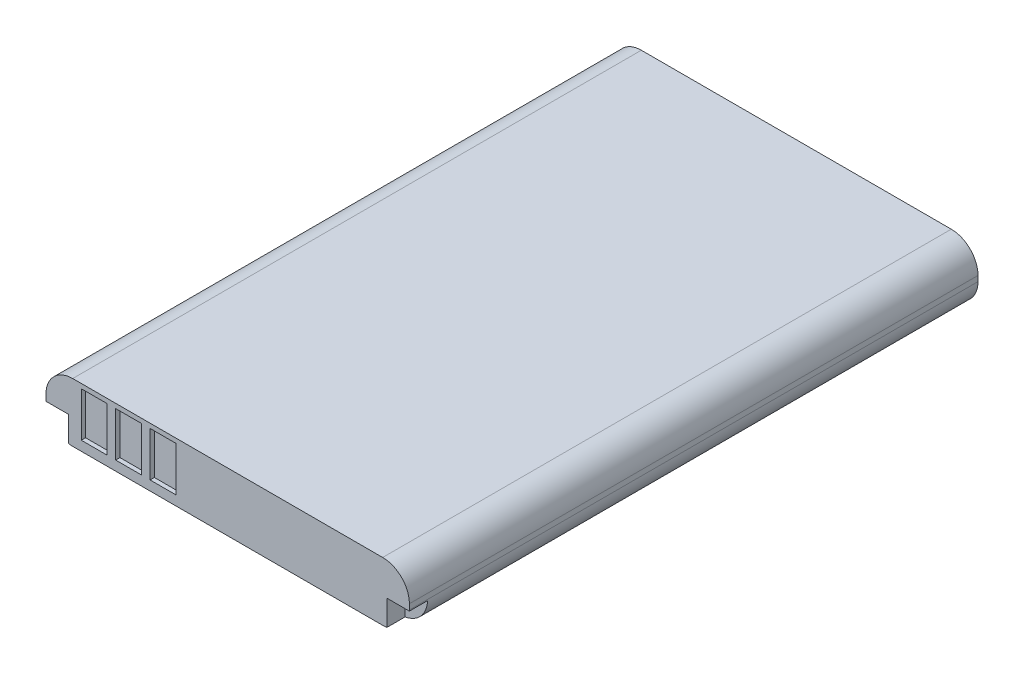
SolidWorks part; units mm, degrees
ref_plane "Front Plane" through (0, 0, 0) normal (0, 0, 1) x (1, 0, 0)
ref_plane "Top Plane" through (0, 0, 0) normal (0, 1, 0) x (1, 0, 0)
ref_plane "Right Plane" through (0, 0, 0) normal (1, 0, 0) x (0, 0, -1)
ref_axis "X-Axis" through (-18.7, 0, 0) along (1, 0, 0)
ref_axis "Y-Axis" through (0, 5.775, 0) along (0, -1, 0)
ref_axis "Z-Axis" through (0, 0, -29.15) along (0, 0, 1)
sketch "Sketch1" plane through (0, 0, 0) normal (0, 1, 0) x (1, 0, 0)
  line L1 (-17, -26.6) -> (17, -26.6)
  line L2 (-17, -26.6) -> (-17, 26.6)
  line L3 (-17, 26.6) -> (17, 26.6)
  line L4 (17, -26.6) -> (17, 26.6)
  line L5 (-17, -26.6) -> (17, 26.6) construction
  line L6 (-17, 26.6) -> (17, -26.6) construction
  point P0 (0, 0)
  dimension "D1" = 53.2
  dimension "D2" = 34
extrude "Boss-Extrude1" add sketch "Sketch1" along normal blind 5.5
fillet "Fillet1" radius 2.5 4 edges at (-17, 0, 0) (-17, 5.5, 0) (17, 0, 0) (17, 5.5, 0)
sketch "Sketch2" plane through (0, 0, 26.6) normal (0, 0, 1) x (1, 0, 0)
  line L0 (-17, 3) -> (-17, 2.5) construction
  line L1 (-11.3, 0.9) -> (-13.7, 0.9)
  line L2 (-11.3, 0.9) -> (-11.3, 5.075)
  line L3 (-11.3, 5.5) -> (-13.7, 5.5) construction
  line L4 (-13.7, 0.9) -> (-13.7, 5.075)
  line L5 (-14.5, 5.5) -> (14.5, 5.5) construction
  line L6 (-13.7, 5.075) -> (-11.3, 5.075)
  line L7 (-13.7, 0.9) -> (-13.7, 5.5) construction
  line L8 (-11.3, 0.9) -> (-11.3, 5.5) construction
  line L9 (-14.5, 0) -> (14.5, 0) construction
  dimension "D1" = 3.3
  dimension "D2" = 2.4
  dimension "D3" = 0.9
  dimension "D4" = 0.85
extrude "Cut-Extrude1" cut sketch "Sketch2" against normal blind 0.4
pattern_linear "LPattern1" count 3 spacing 3.22 along (1, 0, 0) of "Cut-Extrude1"
sketch "Sketch4" plane through (0, 0, 26.6) normal (0, 0, 1) x (1, 0, 0)
  line L1 (-14.9, 0) -> (-19.0322, 0)
  line L2 (-14.9, 0) -> (-14.9, 2.4)
  line L3 (-14.9, 2.4) -> (-19.0322, 2.4)
  line L4 (-19.0322, 0) -> (-19.0322, 2.4)
  line L6 (-19.0322, 0) -> (-14.5, 0) construction
  dimension "D1" = 2.4
  dimension "D2" = 2.1
extrude "Cut-Extrude2" cut sketch "Sketch4" against normal blind 1.7
mirror "Mirror1" about plane through (0, 0, 0) normal (1, 0, 0) of "Cut-Extrude2"
sketch "Sketch5" plane through (0, 0, -26.6) normal (0, 0, -1) x (-1, 0, 0)
  line L0 (-17, 2.75) -> (17, 2.75) construction
  line L1 (-17, 3) -> (-17, 2.5) construction
  line L2 (17, 3) -> (17, 2.5) construction
  line L4 (-9.9, 1.175) -> (9.9, 1.175)
  line L5 (-9.9, 1.175) -> (-9.9, 4.325)
  line L6 (-9.9, 4.325) -> (9.9, 4.325)
  line L7 (9.9, 1.175) -> (9.9, 4.325)
  line L8 (-9.9, 1.175) -> (9.9, 4.325) construction
  line L9 (-9.9, 4.325) -> (9.9, 1.175) construction
  point P6 (0, 2.75)
  dimension "D1" = 3.15
  dimension "D2" = 19.8
extrude "Cut-Extrude3" cut sketch "Sketch5" against normal blind 0.1
equation "\"D3@LPattern1\"=2.4+0.82"
